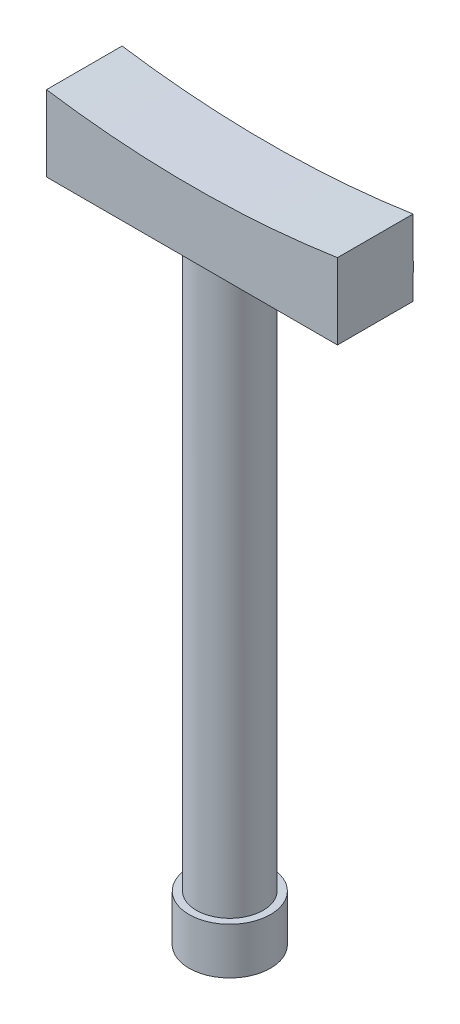
SolidWorks part; units mm, degrees
ref_plane "Front Plane" through (0, 0, 0) normal (0, 0, 1) x (1, 0, 0)
ref_plane "Top Plane" through (0, 0, 0) normal (0, 1, 0) x (1, 0, 0)
ref_plane "Right Plane" through (0, 0, 0) normal (1, 0, 0) x (0, 0, -1)
sketch "Sketch1" plane through (0, 0, 0) normal (0, 1, 0) x (1, 0, 0)
  circle A0 centre (0, 0) radius 7
  circle A1 centre (0, 0) radius 4.75
  circle A2 centre (0, 0) radius 4
  dimension "D1" = 8
  dimension "D2" = 9.5
  dimension "D3" = 14
extrude "Boss-Extrude1" add sketch "Sketch1" along normal blind 8 contours A0 A1 | A1 A2 region at (-6.802, 0, 0) region at (-4.6156, 0, 0)
extrude "Boss-Extrude2" add sketch "Sketch1<3>" along normal blind 80 contours A1 A2 region at (-4.6156, 0, 0)
sketch "Sketch1<3>" plane through (0, 0, 0) normal (0, 1, 0) x (1, 0, 0) same geometry as "Sketch1"
sketch "Sketch3" plane through (0, 0, 0) normal (0, -1, 0) x (1, 0, 0)
  circle A0 centre (0, 0) radius 3.05
  circle A1 centre (0, 0) radius 5.75
  dimension "D1" = 6.1
extrude "Boss-Extrude3" add sketch "Sketch3" against normal blind 105
sketch "Sketch8" plane through (0, 105, 0) normal (0, 1, 0) x (1, 0, 0)
  line L1 (-25, 6.5) -> (25, 6.5)
  line L2 (-25, 6.5) -> (-25, -6.5)
  line L3 (-25, -6.5) -> (25, -6.5)
  line L4 (25, 6.5) -> (25, -6.5)
  line L5 (-25, 6.5) -> (25, -6.5) construction
  line L6 (-25, -6.5) -> (25, 6.5) construction
  point P0 (0, 0)
  dimension "D1" = 50
  dimension "D2" = 13
extrude "Boss-Extrude8" add sketch "Sketch8" along normal blind 4
sketch "Sketch9" plane through (0, 109, 0) normal (0, 1, 0) x (1, 0, 0)
  line L1 (25, -0.254) -> (-25, -0.254)
  line L2 (25, -0.254) -> (25, -6.5)
  line L3 (25, -6.5) -> (-25, -6.5)
  line L4 (-25, -0.254) -> (-25, -6.5)
  line L5 (25, -0.254) -> (-25, -6.5) construction
  line L6 (25, -6.5) -> (-25, -0.254) construction
  point P0 (0, -3.377)
extrude "Boss-Extrude9" add sketch "Sketch9" along normal blind 9
sketch "Sketch10" plane through (-25, 0, 0) normal (-1, 0, 0) x (0, 0, 1)
  line L0 (0.254, 118) -> (0.254, 109)
  line L1 (0.254, 109) -> (-6.5, 109)
  arc A0 (0.254, 118) -> (-6.5, 109) centre (1.377, 110.123) ccw
extrude "Boss-Extrude10" add sketch "Sketch10" against normal blind 50
sketch "Sketch11" plane through (0, 118, 0) normal (0, 1, 0) x (1, 0, 0)
  line L0 (-25, -0.254) -> (-25, -6.5) construction
  line L1 (25, 6.4913) -> (-25, 6.4913)
  line L2 (25, 6.4913) -> (25, -6.4913)
  line L3 (25, -6.4913) -> (-25, -6.4913)
  line L4 (-25, 6.4913) -> (-25, -6.4913)
  line L5 (25, 6.4913) -> (-25, -6.4913) construction
  line L6 (25, -6.4913) -> (-25, 6.4913) construction
  point P0 (0, 0)
extrude "Boss-Extrude11" add sketch "Sketch11" against normal blind 10
sketch "Sketch12" plane through (0, 0, -6.4913) normal (0, 0, -1) x (-1, 0, 0)
  line L0 (-25, 118) -> (25, 118)
  line L1 (-25, 118) -> (25, 118) construction
  line L2 (25, 111.3052) -> (25, 118) construction
  arc A0 (-25, 118) -> (25, 118) centre (0, 283.6596) ccw
extrude "Cut-Extrude1" cut sketch "Sketch12" against normal blind 100
